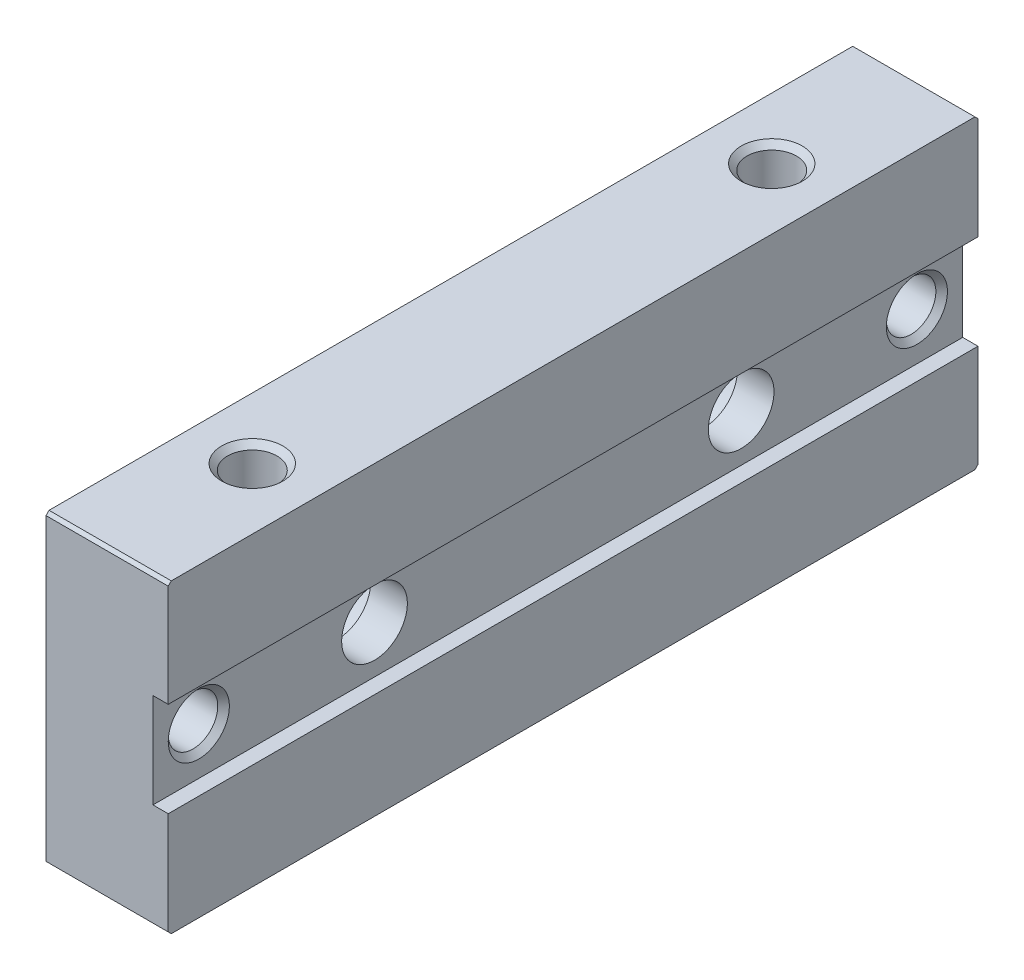
SolidWorks part; units mm, degrees
ref_plane "前视基准面" through (0, 0, 0) normal (0, 0, 1) x (1, 0, 0)
ref_plane "上视基准面" through (0, 0, 0) normal (0, 1, 0) x (1, 0, 0)
ref_plane "右视基准面" through (0, 0, 0) normal (1, 0, 0) x (0, 0, -1)
sketch "草图1" plane through (0, 0, 0) normal (1, 0, 0) x (0, 0, -1)
  line L0 (-26.5, 19.8) -> (-26.5, 0.2)
  line L1 (-26.5, 0.2) -> (-26.3, 0)
  line L2 (-26.3, 0) -> (26.3, 0)
  line L3 (26.3, 0) -> (26.5, 0.2)
  line L4 (26.5, 0.2) -> (26.5, 19.8)
  line L5 (26.5, 19.8) -> (26.3, 20)
  line L6 (26.3, 20) -> (-26.3, 20)
  line L7 (-26.3, 20) -> (-26.5, 19.8)
extrude "凸台-拉伸1" add sketch "草图1" along normal blind 8
ref_plane "基准面1" through (0, 0, 12) normal (0, 0, 1) x (1, 0, 0)
ref_plane "基准面2" through (0, 0, -12) normal (0, 0, 1) x (1, 0, 0)
ref_plane "基准面3" through (0, 0, -17) normal (0, 0, 1) x (1, 0, 0)
sketch "草图2" plane through (0, 0, -17) normal (0, 0, 1) x (1, 0, 0)
  line L0 (4, 20) -> (6, 20)
  line L1 (6, 20) -> (5.621, 19.621)
  line L2 (5.621, 19.621) -> (5.621, 14)
  line L3 (5.621, 14) -> (4, 13.0641)
  line L4 (4, 13.0641) -> (4, 20)
  line L5 (4, 13.0641) -> (4, 20) construction
revolve "切除-旋转1" cut sketch "草图2" angle 360 about L5 reverse direction yes
cosmetic thread "装饰螺纹线1" parameters "D1"=5, "D2"=4
ref_plane "基准面4" through (0, 0, 17) normal (0, 0, 1) x (1, 0, 0)
sketch "草图3" plane through (0, 0, 17) normal (0, 0, 1) x (1, 0, 0)
  line L0 (4, 20) -> (6, 20)
  line L1 (6, 20) -> (5.621, 19.621)
  line L2 (5.621, 19.621) -> (5.621, 14)
  line L3 (5.621, 14) -> (4, 13.0641)
  line L4 (4, 13.0641) -> (4, 20)
  line L5 (4, 13.0641) -> (4, 20) construction
revolve "切除-旋转2" cut sketch "草图3" angle 360 about L5 reverse direction yes
cosmetic thread "装饰螺纹线2" parameters "D1"=5, "D2"=4
sketch "草图4" plane through (0, 0, 0) normal (0, 0, 1) x (1, 0, 0)
  line L0 (7, 6.9) -> (19.4, 6.9)
  line L1 (19.4, 6.9) -> (19.4, 13.1)
  line L2 (19.4, 13.1) -> (7, 13.1)
  line L3 (7, 13.1) -> (7, 6.9)
extrude "切除-拉伸1" cut sketch "草图4" along normal blind 54 and the other way blind 54
ref_plane "基准面5" through (0, 0, 23.5) normal (0, 0, 1) x (1, 0, 0)
sketch "草图5" plane through (0, 0, 23.5) normal (0, 0, 1) x (1, 0, 0)
  line L0 (0, 10) -> (0, 12)
  line L1 (0, 12) -> (0.379, 11.621)
  line L2 (0.379, 11.621) -> (6.621, 11.621)
  line L3 (6.621, 11.621) -> (7, 12)
  line L4 (7, 12) -> (7, 10)
  line L5 (7, 10) -> (0, 10)
  line L6 (7, 10) -> (0, 10) construction
revolve "切除-旋转3" cut sketch "草图5" angle 360 about L6 reverse direction yes
cosmetic thread "装饰螺纹线3" parameters "D1"=7, "D2"=4
ref_plane "基准面6" through (0, 0, -23.5) normal (0, 0, 1) x (1, 0, 0)
sketch "草图6" plane through (0, 0, -23.5) normal (0, 0, 1) x (1, 0, 0)
  line L0 (0, 10) -> (0, 12)
  line L1 (0, 12) -> (0.379, 11.621)
  line L2 (0.379, 11.621) -> (6.621, 11.621)
  line L3 (6.621, 11.621) -> (7, 12)
  line L4 (7, 12) -> (7, 10)
  line L5 (7, 10) -> (0, 10)
  line L6 (7, 10) -> (0, 10) construction
revolve "切除-旋转4" cut sketch "草图6" angle 360 about L6 reverse direction yes
cosmetic thread "装饰螺纹线4" parameters "D1"=7, "D2"=4
ref_plane "基准面7" through (0, 0, 12) normal (0, 0, 1) x (1, 0, 0)
sketch "草图7" plane through (0, 0, 12) normal (0, 0, 1) x (1, 0, 0)
  line L0 (0, 10) -> (0, 13.9)
  line L1 (0, 13.9) -> (4.6, 13.9)
  line L2 (4.6, 13.9) -> (4.6, 12.15)
  line L3 (4.6, 12.15) -> (7, 12.15)
  line L4 (7, 12.15) -> (7, 10)
  line L5 (7, 10) -> (0, 10)
  line L6 (7, 10) -> (0, 10) construction
revolve "切除-旋转5" cut sketch "草图7" angle 360 about L6 reverse direction yes
ref_plane "基准面8" through (0, 0, -12) normal (0, 0, 1) x (1, 0, 0)
sketch "草图8" plane through (0, 0, -12) normal (0, 0, 1) x (1, 0, 0)
  line L0 (0, 10) -> (0, 13.9)
  line L1 (0, 13.9) -> (4.6, 13.9)
  line L2 (4.6, 13.9) -> (4.6, 12.15)
  line L3 (4.6, 12.15) -> (7, 12.15)
  line L4 (7, 12.15) -> (7, 10)
  line L5 (7, 10) -> (0, 10)
  line L6 (7, 10) -> (0, 10) construction
revolve "切除-旋转6" cut sketch "草图8" angle 360 about L6 reverse direction yes
ref_plane "基准面9" through (7, 0, 0) normal (1, 0, 0) x (0, 0, -1)
ref_plane "基准面10" through (4.6, 0, 0) normal (1, 0, 0) x (0, 0, -1)
ref_plane "for_body XY" through (0, 0, 0) normal (-1, 0, 0) x (0, 0, 1)
ref_plane "for_body XZ" through (0, 10, 0) normal (0, 1, 0) x (1, 0, 0)
ref_plane "for_body YZ" through (0, 0, 0) normal (0, 0, -1) x (-1, 0, 0)
ref_axis "for_body X" through (0, 10, 80.9) along (0, 0, -1)
ref_axis "for_body Y" through (0, 50, 0) along (0, -1, 0)
ref_axis "for_body Z" through (-80.9, 10, 0) along (1, 0, 0)
sketch3d "for_body"
  point P0 (0, 10, 0)
ref_plane "fpr_rod_r XY" through (7, 0, 0) normal (-1, 0, 0) x (0, 0, 1)
ref_plane "fpr_rod_r XZ" through (0, 10, 0) normal (0, 1, 0) x (1, 0, 0)
ref_plane "fpr_rod_r YZ" through (0, 0, -12) normal (0, 0, -1) x (-1, 0, 0)
ref_axis "fpr_rod_r X" through (7, 10, 80.9) along (0, 0, -1)
ref_axis "fpr_rod_r Y" through (7, 50, -12) along (0, -1, 0)
ref_axis "fpr_rod_r Z" through (-80.9, 10, -12) along (1, 0, 0)
sketch3d "fpr_rod_r"
  point P0 (7, 10, -12)
ref_plane "fpr_rod_l XY" through (7, 0, 0) normal (-1, 0, 0) x (0, 0, 1)
ref_plane "fpr_rod_l XZ" through (0, 10, 0) normal (0, 1, 0) x (1, 0, 0)
ref_plane "fpr_rod_l YZ" through (0, 0, 12) normal (0, 0, -1) x (-1, 0, 0)
ref_axis "fpr_rod_l X" through (7, 10, 80.9) along (0, 0, -1)
ref_axis "fpr_rod_l Y" through (7, 50, 12) along (0, -1, 0)
ref_axis "fpr_rod_l Z" through (-80.9, 10, 12) along (1, 0, 0)
sketch3d "fpr_rod_l"
  point P0 (7, 10, 12)
ref_plane "fpr_screw_l XY" through (4.6, 0, 0) normal (-1, 0, 0) x (0, 0, 1)
ref_plane "fpr_screw_l XZ" through (0, 10, 0) normal (0, 1, 0) x (1, 0, 0)
ref_plane "fpr_screw_l YZ" through (0, 0, 12) normal (0, 0, -1) x (-1, 0, 0)
ref_axis "fpr_screw_l X" through (4.6, 10, 80.9) along (0, 0, -1)
ref_axis "fpr_screw_l Y" through (4.6, 50, 12) along (0, -1, 0)
ref_axis "fpr_screw_l Z" through (-80.9, 10, 12) along (1, 0, 0)
sketch3d "fpr_screw_l"
  point P0 (4.6, 10, 12)
ref_plane "fpr_screw_r XY" through (4.6, 0, 0) normal (-1, 0, 0) x (0, 0, 1)
ref_plane "fpr_screw_r XZ" through (0, 10, 0) normal (0, 1, 0) x (1, 0, 0)
ref_plane "fpr_screw_r YZ" through (0, 0, -12) normal (0, 0, -1) x (-1, 0, 0)
ref_axis "fpr_screw_r X" through (4.6, 10, 80.9) along (0, 0, -1)
ref_axis "fpr_screw_r Y" through (4.6, 50, -12) along (0, -1, 0)
ref_axis "fpr_screw_r Z" through (-80.9, 10, -12) along (1, 0, 0)
sketch3d "fpr_screw_r"
  point P0 (4.6, 10, -12)
